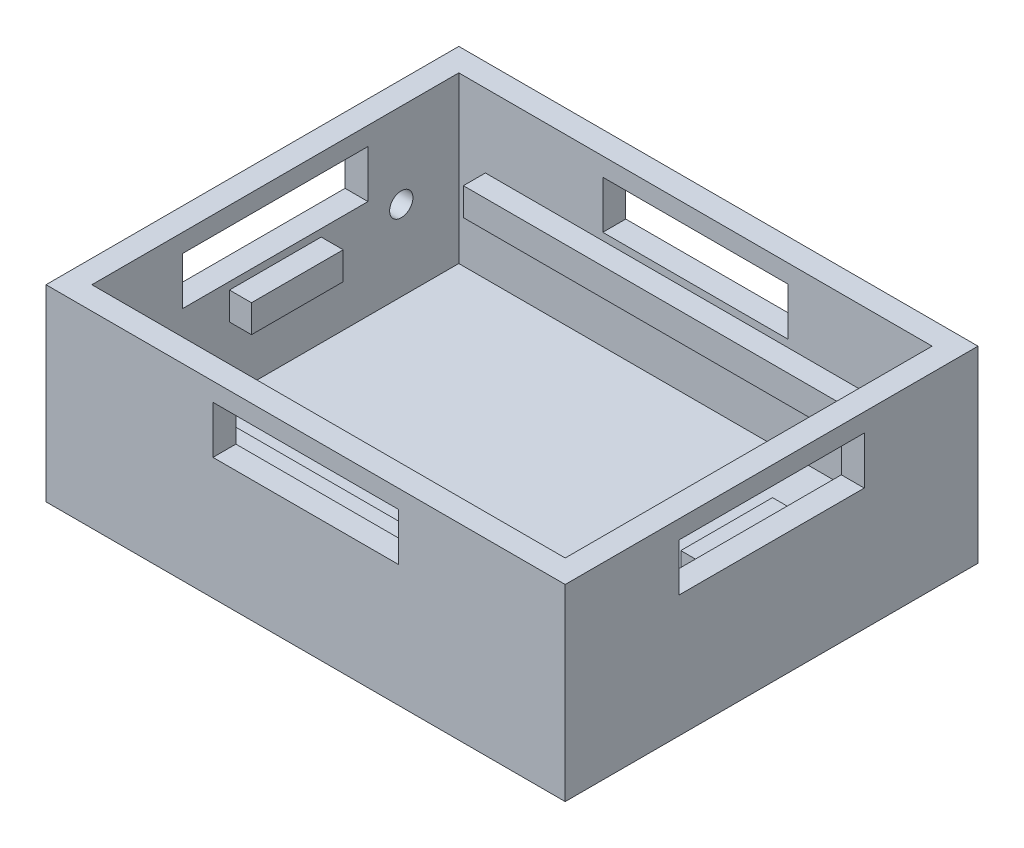
SolidWorks part; units mm, degrees
ref_plane "Front Plane" through (0, 0, 0) normal (0, 0, 1) x (1, 0, 0)
ref_plane "Top Plane" through (0, 0, 0) normal (0, 1, 0) x (1, 0, 0)
ref_plane "Right Plane" through (0, 0, 0) normal (1, 0, 0) x (0, 0, -1)
sketch "Sketch1" plane through (0, 0, 0) normal (0, 1, 0) x (1, 0, 0)
  line L0 (-2.5, 2.5) -> (-2.5, 202.5)
  line L5 (-15, -10) -> (268, -10)
  line L6 (-15, -10) -> (-15, 215)
  line L7 (-15, 215) -> (268, 215)
  line L8 (268, -10) -> (268, 215)
  line L9 (-2.5, 202.5) -> (255.5, 202.5)
  line L10 (255.5, 2.5) -> (255.5, 202.5)
  line L11 (-2.5, 2.5) -> (255.5, 2.5)
  dimension "D1" = 283
  dimension "D2" = 225
  dimension "D3" = 12.5
extrude "Walls" add sketch "Sketch1" along normal blind 90
sketch "Sketch3" plane through (0, 0, 0) normal (0, -1, 0) x (1, 0, 0)
  line L0 (268, -215) -> (-15, -215) construction
  line L1 (268, 10) -> (268, -215) construction
  line L2 (-15, 10) -> (268, 10) construction
  line L3 (-15, -215) -> (-15, 10) construction
  line L4 (268, -215) -> (-15, -215)
  line L5 (268, 10) -> (268, -215)
  line L6 (-15, 10) -> (268, 10)
  line L7 (-15, -215) -> (-15, 10)
extrude "Base" add sketch "Sketch3" along normal blind 12.5
ref_plane "Long_Support_Midplane" through (126.5, 0, 0) normal (1, 0, 0) x (0, 0, -1)
sketch "Sketch4" plane through (126.5, 0, 0) normal (1, 0, 0) x (0, 0, -1)
  line L0 (2.5, 0) -> (2.5, 90)
  line L1 (2.5, 50) -> (14.5, 50)
  line L2 (2.5, 50) -> (2.5, 34.9)
  line L3 (2.5, 34.9) -> (14.5, 34.9)
  line L4 (14.5, 50) -> (14.5, 34.9)
  line L5 (2.5, 0) -> (2.5, 90) construction
  line L6 (202.5, 50) -> (190.5, 50)
  line L7 (202.5, 50) -> (202.5, 34.9)
  line L8 (202.5, 34.9) -> (190.5, 34.9)
  line L9 (190.5, 50) -> (190.5, 34.9)
  line L14 (2.5, 0) -> (202.5, 0)
  line L15 (202.5, 0) -> (202.5, 90)
  line L16 (202.5, 90) -> (2.5, 90)
  line L17 (2.5, 90) -> (2.5, 0)
  line L18 (2.5, 0) -> (202.5, 0) construction
  line L19 (202.5, 0) -> (202.5, 90) construction
  line L20 (202.5, 90) -> (2.5, 90) construction
  line L21 (2.5, 90) -> (2.5, 0) construction
  dimension "D1" = 15.1
  dimension "D2" = 12
  dimension "D4" = 50
extrude "Long_Support" add sketch "Sketch4" along normal mid plane 229
ref_plane "Short_Support_Midplane" through (0, 0, -102.5) normal (0, 0, -1) x (-1, 0, 0)
sketch "Sketch5" plane through (0, 0, -102.5) normal (0, 0, -1) x (-1, 0, 0)
  line L1 (-255.5, 50) -> (-243.5, 50)
  line L2 (-255.5, 50) -> (-255.5, 34.9)
  line L3 (-255.5, 34.9) -> (-243.5, 34.9)
  line L4 (-243.5, 50) -> (-243.5, 34.9)
  line L5 (2.5, 50) -> (-9.5, 50)
  line L6 (2.5, 50) -> (2.5, 34.9)
  line L7 (2.5, 34.9) -> (-9.5, 34.9)
  line L8 (-9.5, 50) -> (-9.5, 34.9)
  line L12 (-255.5, 0) -> (2.5, 0)
  line L13 (2.5, 0) -> (2.5, 90)
  line L14 (2.5, 90) -> (-255.5, 90)
  line L15 (2.5, 0) -> (2.5, 90) construction
  line L16 (-255.5, 0) -> (2.5, 0) construction
  line L20 (-255.5, 90) -> (-255.5, 0)
  line L21 (-255.5, 90) -> (-255.5, 0) construction
  line L22 (2.5, 90) -> (-255.5, 90) construction
  dimension "D4" = 50
  dimension "D2" = 15.1
extrude "Short_Support" add sketch "Sketch5" along normal mid plane 50
sketch "Sketch6" plane through (-2.5, 0, 0) normal (1, 0, 0) x (0, 0, -1)
  line L4 (2.5, 0) -> (202.5, 0)
  line L5 (202.5, 0) -> (202.5, 90)
  line L6 (202.5, 90) -> (2.5, 90)
  line L7 (2.5, 90) -> (2.5, 0)
  line L8 (2.5, 0) -> (202.5, 0) construction
  line L9 (202.5, 0) -> (202.5, 90) construction
  line L10 (202.5, 90) -> (2.5, 90) construction
  line L11 (2.5, 90) -> (2.5, 0) construction
  circle A0 centre (171.15, 43.65) radius 6.35
  dimension "D2" = 12.7
  dimension "D3" = 31.35
  dimension "D4" = 43.65
extrude "Reservoir_Outflow_Tube_Hole" cut sketch "Sketch6" against normal up to next
sketch "Sketch7" plane through (-2.5, 0, 0) normal (1, 0, 0) x (0, 0, -1)
  line L0 (127.5, 50) -> (77.5, 50) construction
  line L1 (52, 54) -> (153, 54)
  line L2 (52, 54) -> (52, 80)
  line L3 (52, 80) -> (153, 80)
  line L4 (153, 54) -> (153, 80)
  line L5 (202.5, 90) -> (2.5, 90) construction
  line L7 (102.5, 80) -> (102.5, 54) construction
  line L8 (102.5, -27.5) -> (102.5, 27.5) construction
  dimension "D1" = 4
  dimension "D2" = 10
  dimension "D3" = 26
  dimension "D4" = 101
extrude "Connector_Port_ShortSide" cut sketch "Sketch7" against normal up to surface (12.5 mm away) up to face at (-15, 43.65, -177.5)
pattern_linear "LPattern1" count 2 spacing 270.5 along (1, 0, 0) of "Connector_Port_ShortSide"
sketch "Sketch8" plane through (0, 0, -2.5) normal (0, 0, 1) x (1, 0, 0)
  line L1 (76, 54) -> (177, 54)
  line L2 (76, 54) -> (76, 80)
  line L3 (76, 80) -> (177, 80)
  line L4 (177, 54) -> (177, 80)
  line L6 (241, 50) -> (12, 50) construction
  line L7 (126.5, 80) -> (126.5, 54) construction
  line L9 (-2.5, 90) -> (255.5, 90) construction
  line L10 (126.5, -28.05) -> (126.5, 28.05) construction
  dimension "D3" = 26
  dimension "D4" = 101
  dimension "D1" = 4
  dimension "D2" = 10
extrude "Connector_Port_LongSide" cut sketch "Sketch8" along normal up to surface (12.5 mm away) contours L4 L3 L2 L1 up to face at (126.5, 38.75, 10)
pattern_linear "LPattern2" count 2 spacing 212.5 along (0, 0, -1) of "Connector_Port_LongSide"
equation "\"Length\"= 283"
equation "\"Width\"= 225"
equation "\"WallThickness\"= 12.5"
equation "\"UpperWaterJacketThickness\"= 28"
equation "\"SpacerHeight\"= 80.2"
equation "\"PlateLength\"=252"
equation "\"PlateWidth\"=190"
equation "\"PlateHoleDiameter\"=5.9"
equation "\"PlateHoleBottom\"= 2"
equation "\"PlateHoleSide\"= 1.55"
equation "\"PlateHoleSpacing\"= 3.1"
equation "\"PlateThickness\"=1.55"
equation "\"D1@Sketch1\"=\"Length\""
equation "\"D2@Sketch1\"=\"Width\""
equation "\"D3@Sketch1\"=\"WallThickness\""
equation "\"ReservoirBottom\"=12.5"
equation "\"D1@Base\"=\"ReservoirBottom\""
equation "\"ReservoirSupportWidth\"=12"
equation "\"D2@Sketch4\"=\"ReservoirSupportWidth\""
equation "\"ReservoirSupportHeight\"=15.1"
equation "\"D1@Sketch4\"=\"ReservoirSupportHeight\""
equation "\"D1@Sketch5\"=\"ReservoirSupportWidth\""
equation "\"D2@Sketch5\"=\"ReservoirSupportHeight\""
equation "\"ReservoirSupportPlacementHeight\"=50"
equation "\"D4@Sketch5\"=\"ReservoirSupportPlacementHeight\""
equation "\"D4@Sketch4\"=\"ReservoirSupportPlacementHeight\""
equation "\"ReservoirHoleDiameter\"=12.7"
equation "\"D2@Sketch6\"=\"ReservoirHoleDiameter\""
equation "\"ReservoirHoleRight\"= 25"
equation "\"D3@Sketch6\"=\"ReservoirHoleRight\"+\"ReservoirHoleDiameter\"/2"
equation "\"ReservoirHoleTop\"= \"ReservoirSupportPlacementHeight\""
equation "\"D4@Sketch6\"=\"ReservoirHoleTop\"-\"ReservoirHoleDiameter\"/2"
equation "\"ReservoirHeight\"=90"
equation "\"D1@Walls\"=\"ReservoirHeight\""
equation "\"ReservoirPortBottom\"=4"
equation "\"D1@Sketch7\"=\"ReservoirPortBottom\""
equation "\"ReservoirPortTop\"= 10"
equation "\"D2@Sketch7\"=\"ReservoirPortTop\""
equation "\"ReservoirPortWidth\"=101"
equation "\"D4@Sketch7\"=\"ReservoirPortWidth\""
equation "\"D4@Sketch8\"=\"ReservoirPortWidth\""
equation "\"D1@Sketch8\"=\"ReservoirPortBottom\""
equation "\"D2@Sketch8\"=\"ReservoirPortTop\""
